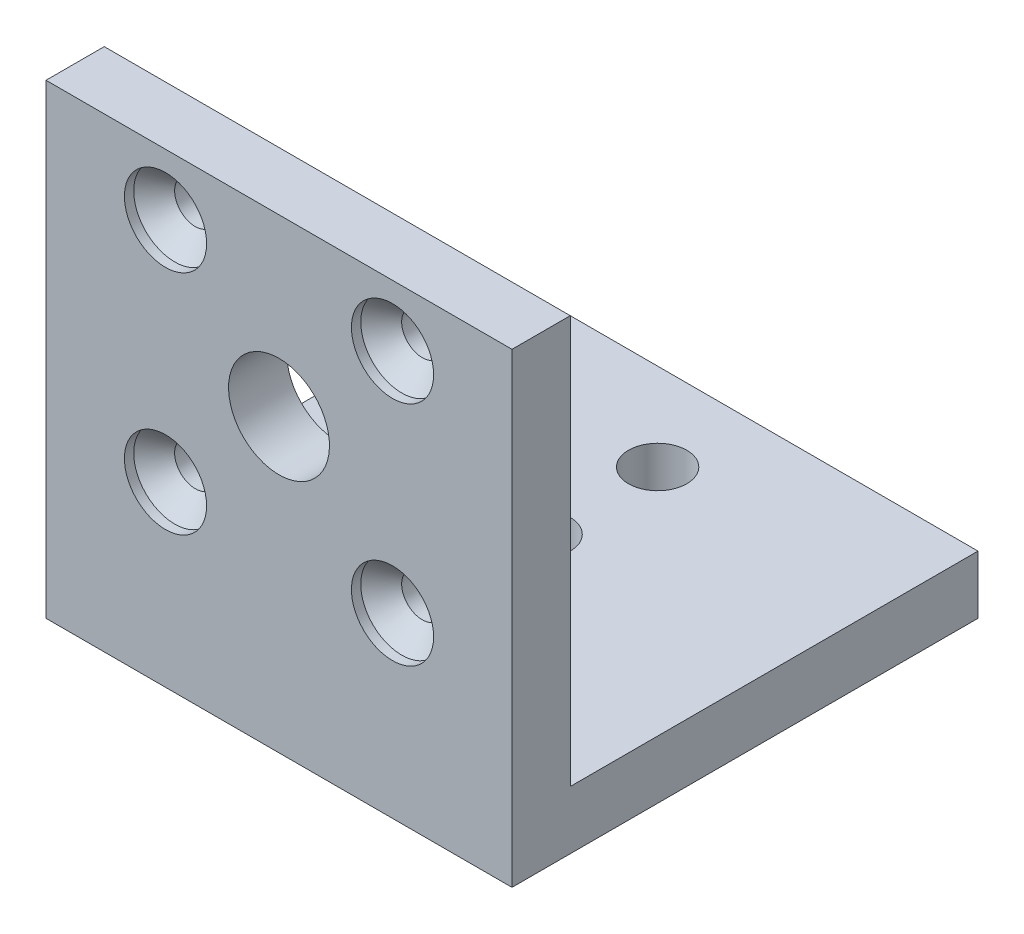
SolidWorks part; units mm, degrees
ref_plane "Front Plane" through (0, 0, 0) normal (0, 0, 1) x (1, 0, 0)
ref_plane "Top Plane" through (0, 0, 0) normal (0, 1, 0) x (1, 0, 0)
ref_plane "Right Plane" through (0, 0, 0) normal (1, 0, 0) x (0, 0, -1)
sketch "Sketch1" plane through (0, 0, 0) normal (1, 0, 0) x (0, 0, -1)
  line L0 (0, 0) -> (0, -44.45)
  line L1 (0, -44.45) -> (44.45, -44.45)
  line L2 (-6.35, 0) -> (-6.35, -50.8)
  line L3 (-6.35, -50.8) -> (44.45, -50.8)
  line L4 (-6.35, 0) -> (0, 0)
  line L5 (44.45, -44.45) -> (44.45, -50.8)
  dimension "D2" = 50.8
  dimension "D3" = 50.8
  dimension "D1" = 6.35
extrude "Boss-Extrude1" add sketch "Sketch1" along normal blind 50.8
sketch "Sketch2" plane through (0, 0, 0) normal (0, 0, -1) x (-1, 0, 0)
  line L1 (-50.8, 0) -> (0, 0) construction
  line L2 (-13.0256, -6.6756) -> (-37.7744, -6.6756) construction
  line L3 (-50.8, -44.45) -> (-50.8, 0) construction
  circle A0 centre (-13.0256, -6.6756) radius 2.25
  circle A1 centre (-13.0256, -31.4244) radius 2.25
  circle A2 centre (-37.7744, -31.4244) radius 2.25
  circle A3 centre (-37.7744, -6.6756) radius 2.25
  circle A4 centre (-25.4, -19.05) radius 5.5
  point P3 (-50.8, -22.225)
  point P12 (-25.4, -19.05)
  dimension "D1" = 17.5
  dimension "D2" = 4.5
  dimension "D7" = 11
  dimension "D4" = 25.4
  dimension "D5" = 19.05
  dimension "D6" = 0
  dimension "D3" = 4
extrude "Cut-Extrude1" cut sketch "Sketch2" against normal up to next
sketch "Sketch4" plane through (0, -44.45, 0) normal (0, 1, 0) x (1, 0, 0)
  line L0 (0, 44.45) -> (0, 0) construction
  line L1 (50.8, 44.45) -> (0, 44.45) construction
  line L2 (50.8, 44.45) -> (50.8, 0) construction
  circle A0 centre (25.4, 34.925) radius 3.175
  circle A1 centre (25.4, 22.225) radius 3.175
  dimension "D1" = 6.35
  dimension "D2" = 6.35
  dimension "D3" = 25.4
  dimension "D4" = 22.225
  dimension "D5" = 9.525
  dimension "D6" = 25.4
extrude "Cut-Extrude2" cut sketch "Sketch4" against normal up to next
hole_wizard "CSK for M4 SFHCS1" positions "Sketch6" profile "Sketch5" countersink size "M4" standard "ANSI Metric" end condition through all
sketch "Sketch6" plane through (0, 0, 6.35) normal (0, 0, 1) x (1, 0, 0)
  point P0 (13.0256, -6.6756)
  point P3 (37.7744, -6.6756)
  point P6 (37.7744, -31.4244)
  point P9 (13.0256, -31.4244)
sketch "Sketch5" plane through (13.0256, -6.6756, 6.35) normal (1, 0, 0) x (0, -1, 0)
  line L0 (0, 0) -> (0, 50.8)
  line L1 (0, 50.8) -> (2.15, 50.8)
  line L2 (2.15, 50.8) -> (2.15, 3.346)
  line L3 (2.15, 3.346) -> (4.48, 1.016)
  line L4 (4.48, 1.016) -> (4.48, 0)
  line L6 (4.48, 0) -> (0, 0)
  line L7 (-2.15, 3.346) -> (-4.48, 1.016) construction
  line L11 (0, -6.35) -> (0, 107.95) construction
  dimension "Thru Hole Dia." = 4.3
  dimension "Thru Hole Depth" = 50.8
  dimension "C'Sink Dia." = 8.96
  dimension "C'Sink Angle" = 90
  dimension "Head Clearance" = 1.016
